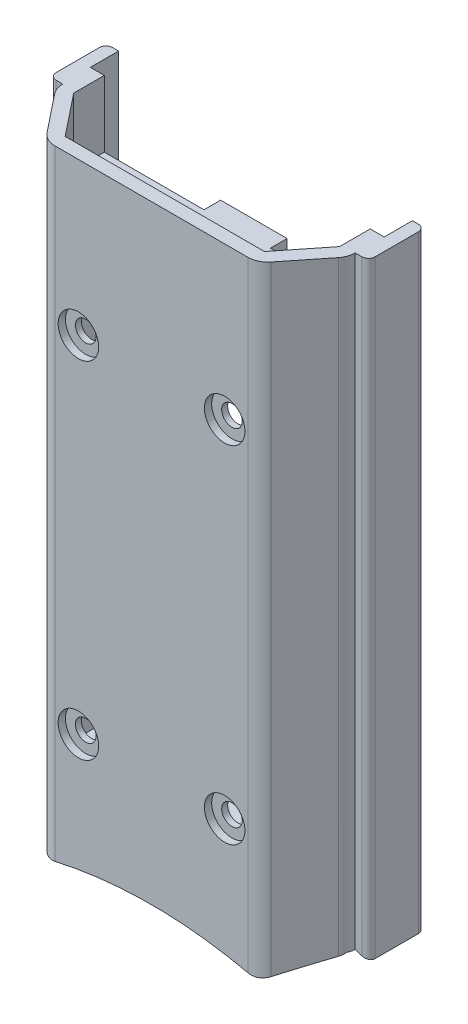
SolidWorks part; units mm, degrees
ref_plane "前视基准面" through (0, 0, 0) normal (0, 0, 1) x (1, 0, 0)
ref_plane "上视基准面" through (0, 0, 0) normal (0, 1, 0) x (1, 0, 0)
ref_plane "右视基准面" through (0, 0, 0) normal (1, 0, 0) x (0, 0, -1)
other "Configuration Table"
sketch "草图1" plane through (0, 0, 0) normal (0, 1, 0) x (1, 0, 0)
  line L5 (21.3466, -10.7196) -> (16.852, -16.3628)
  line L7 (20, -4.6001) -> (22, -4.6001)
  line L9 (20, -9.2001) -> (20, -4.6001)
  line L10 (14.9873, -15.4937) -> (20, -9.2001)
  line L11 (14.5054, -17.4937) -> (-14.5054, -17.4937)
  line L12 (-14.9873, -15.4937) -> (14.9873, -15.4937)
  line L14 (-20, -9.2001) -> (-14.9873, -15.4937)
  line L15 (-20, -4.6001) -> (-20, -9.2001)
  line L17 (-22.1, -0.3496) -> (-23, -0.3496)
  line L18 (-24, -1.3496) -> (-24, -7.8505)
  line L20 (-22, -4.6001) -> (-22.1, -4.6001)
  line L21 (-22.1, -4.6001) -> (-22.1, -0.3496)
  line L22 (22.1, -0.3496) -> (23, -0.3496)
  line L23 (24, -1.3496) -> (24, -7.8505)
  line L41 (22, -4.6001) -> (22.1, -4.6001)
  line L42 (22.1, -4.6001) -> (22.1, -0.3496)
  line L43 (-16.852, -16.3628) -> (-21.3466, -10.7196)
  line L57 (-22, -4.6001) -> (-20, -4.6001)
  line L59 (-22, -8.8505) -> (-23, -8.8505)
  line L61 (22, -8.8505) -> (23, -8.8505)
  arc A2 (23, -8.8505) -> (24, -7.8505) centre (23, -7.8505) ccw
  arc A3 (24, -1.3496) -> (23, -0.3496) centre (23, -1.3496) ccw
  arc A12 (16.852, -16.3628) -> (14.5054, -17.4937) centre (14.5054, -14.4937) cw
  arc A14 (-14.5054, -17.4937) -> (-16.852, -16.3628) centre (-14.5054, -14.4937) cw
  arc A16 (-23, -8.8505) -> (-24, -7.8505) centre (-23, -7.8505) cw
  arc A17 (-23, -0.3496) -> (-24, -1.3496) centre (-23, -1.3496) ccw
  arc A19 (21.3466, -10.7196) -> (22, -8.8505) centre (19, -8.8505) ccw
  arc A20 (-22, -8.8505) -> (-21.3466, -10.7196) centre (-19, -8.8505) ccw
  dimension "D3" = 0.1
  dimension "D2" = 0.1
extrude "凸台-拉伸1" add sketch "草图1" along normal up to surface (58.8974 mm away)
sketch "草图2" plane through (0, 0, 0) normal (0, -1, 0) x (1, 0, 0)
  line L18 (23, 8.8505) -> (22, 8.8505)
  line L19 (-24, 7.8505) -> (-24, 1.3496)
  line L20 (-23, 0.3496) -> (-22.1, 0.3496)
  line L21 (-22.1, 0.3496) -> (-22.1, 4.6001)
  line L22 (-22.1, 4.6001) -> (-20, 4.6001)
  line L23 (-20, 4.6001) -> (-20, 9.2001)
  line L24 (-20, 9.2001) -> (-14.9873, 15.4937)
  line L25 (-14.9873, 15.4937) -> (14.9873, 15.4937)
  line L26 (14.9873, 15.4937) -> (20, 9.2001)
  line L27 (20, 9.2001) -> (20, 4.6001)
  line L28 (20, 4.6001) -> (22.1, 4.6001)
  line L29 (22.1, 4.6001) -> (22.1, 0.3496)
  line L30 (22.1, 0.3496) -> (23, 0.3496)
  line L31 (24, 1.3496) -> (24, 7.8505)
  line L32 (23, 8.8505) -> (22, 8.8505)
  line L33 (21.3466, 10.7196) -> (16.852, 16.3628)
  line L34 (14.5054, 17.4937) -> (-14.5054, 17.4937)
  line L37 (-24, 7.8505) -> (-24, 1.3496)
  line L38 (-23, 0.3496) -> (-22.1, 0.3496)
  line L39 (-22.1, 0.3496) -> (-22.1, 4.6001)
  line L40 (-22.1, 4.6001) -> (-20, 4.6001)
  line L41 (-20, 4.6001) -> (-20, 9.2001)
  line L42 (-20, 9.2001) -> (-14.9873, 15.4937)
  line L43 (-14.9873, 15.4937) -> (14.9873, 15.4937)
  line L44 (14.9873, 15.4937) -> (20, 9.2001)
  line L45 (20, 9.2001) -> (20, 4.6001)
  line L46 (20, 4.6001) -> (22.1, 4.6001)
  line L47 (22.1, 4.6001) -> (22.1, 0.3496)
  line L48 (22.1, 0.3496) -> (23, 0.3496)
  line L49 (24, 1.3496) -> (24, 7.8505)
  line L51 (21.3466, 10.7196) -> (16.852, 16.3628)
  line L52 (14.5054, 17.4937) -> (-14.5054, 17.4937)
  line L57 (-16.852, 16.3628) -> (-21.3466, 10.7196)
  line L58 (-16.852, 16.3628) -> (-21.3466, 10.7196)
  line L61 (-22, 8.8505) -> (-23, 8.8505)
  line L62 (-22, 8.8505) -> (-23, 8.8505)
  arc A8 (-21.3466, 10.7196) -> (-22, 8.8505) centre (-19, 8.8505) ccw
  arc A9 (-21.3466, 10.7196) -> (-22, 8.8505) centre (-19, 8.8505) ccw
  arc A10 (22, 8.8505) -> (21.3466, 10.7196) centre (19, 8.8505) ccw
  arc A11 (22, 8.8505) -> (21.3466, 10.7196) centre (19, 8.8505) ccw
  arc A12 (-23, 8.8505) -> (-24, 7.8505) centre (-23, 7.8505) ccw
  arc A13 (-24, 1.3496) -> (-23, 0.3496) centre (-23, 1.3496) ccw
  arc A14 (23, 0.3496) -> (24, 1.3496) centre (23, 1.3496) ccw
  arc A15 (24, 7.8505) -> (23, 8.8505) centre (23, 7.8505) ccw
  arc A18 (16.852, 16.3628) -> (14.5054, 17.4937) centre (14.5054, 14.4937) ccw
  arc A19 (-14.5054, 17.4937) -> (-16.852, 16.3628) centre (-14.5054, 14.4937) ccw
  arc A22 (-23, 8.8505) -> (-24, 7.8505) centre (-23, 7.8505) ccw
  arc A23 (-24, 1.3496) -> (-23, 0.3496) centre (-23, 1.3496) ccw
  arc A24 (23, 0.3496) -> (24, 1.3496) centre (23, 1.3496) ccw
  arc A25 (24, 7.8505) -> (23, 8.8505) centre (23, 7.8505) ccw
  arc A28 (16.852, 16.3628) -> (14.5054, 17.4937) centre (14.5054, 14.4937) ccw
  arc A29 (-14.5054, 17.4937) -> (-16.852, 16.3628) centre (-14.5054, 14.4937) ccw
  dimension "D1" = 0
extrude "凸台-拉伸2" add sketch "草图2" along normal up to surface (38.3996 mm away)
ref_plane "基准面1" through (0, -38.3996, 0) normal (0, -1, 0) x (-1, 0, 0)
sketch "草图3" plane through (0, 0, 4.6001) normal (0, 0, -1) x (-1, 0, 0)
  line L0 (22.1, -38.3996) -> (22.1, -35.3996)
  line L1 (22.1, 58.8974) -> (22.1, -38.3996) construction
  line L2 (22.1, -35.3996) -> (-22.1, -35.3996)
  line L3 (-22.1, 58.8974) -> (-22.1, -38.3996) construction
  line L4 (-22.1, -35.3996) -> (-22.1, -38.3996)
  line L5 (-22.1, -38.3996) -> (22.1, -38.3996)
  dimension "D1" = 3
extrude "凸台-拉伸3" add sketch "草图3" against normal up to surface (12.8937 mm away) up to face at (0, 10.2489, 17.4937)
sketch "草图4" plane through (0, 0, 4.6001) normal (0, 0, -1) x (-1, 0, 0)
  line L0 (22.1, 38.8974) -> (-22.1, 38.8974)
  line L3 (22.1, 58.8974) -> (22.1, -38.3996) construction
  line L4 (22.1, 38.8974) -> (22.1, 35.8974)
  line L7 (-22.1, 58.8974) -> (-22.1, -38.3996) construction
  line L8 (-22.1, 38.8974) -> (-22.1, 35.8974)
  line L9 (-22.1, 35.8974) -> (22.1, 35.8974)
  dimension "D2" = 3
extrude "凸台-拉伸4" add sketch "草图4" against normal up to surface (12.8937 mm away) up to face at (0, -12.5754, 17.4937)
sketch "草图5" plane through (0, 38.8974, 0) normal (0, 1, 0) x (1, 0, 0)
  line L3 (-22, -8.8505) -> (-22.1, -8.8505)
  line L4 (-22.1, -8.8505) -> (-22.1, -17.4937)
  line L5 (-22.1, -17.4937) -> (-14.5054, -17.4937)
  line L7 (-22.1, -8.8505) -> (-22.1, -17.4937)
  line L8 (-22.1, -17.4937) -> (-14.5054, -17.4937)
  line L9 (14.5054, -17.4937) -> (22.1, -17.4937)
  line L10 (22.1, -17.4937) -> (22.1, -8.8505)
  line L11 (21.3466, -10.7196) -> (16.852, -16.3628)
  line L12 (14.5054, -17.4937) -> (22.1, -17.4937)
  line L13 (22.1, -17.4937) -> (22.1, -8.8505)
  line L14 (21.3466, -10.7196) -> (16.852, -16.3628)
  line L17 (-22, -8.8505) -> (-22.1, -8.8505)
  line L18 (-16.852, -16.3628) -> (-21.3466, -10.7196)
  line L19 (-16.852, -16.3628) -> (-21.3466, -10.7196)
  line L22 (22.1, -8.8505) -> (22, -8.8505)
  line L23 (22.1, -8.8505) -> (22, -8.8505)
  arc A2 (-22, -8.8505) -> (-21.3466, -10.7196) centre (-19, -8.8505) ccw
  arc A3 (-16.852, -16.3628) -> (-14.5054, -17.4937) centre (-14.5054, -14.4937) ccw
  arc A4 (-22, -8.8505) -> (-21.3466, -10.7196) centre (-19, -8.8505) ccw
  arc A5 (21.3466, -10.7196) -> (22, -8.8505) centre (19, -8.8505) ccw
  arc A6 (-16.852, -16.3628) -> (-14.5054, -17.4937) centre (-14.5054, -14.4937) ccw
  arc A9 (14.5054, -17.4937) -> (16.852, -16.3628) centre (14.5054, -14.4937) ccw
  arc A10 (21.3466, -10.7196) -> (22, -8.8505) centre (19, -8.8505) ccw
  arc A12 (14.5054, -17.4937) -> (16.852, -16.3628) centre (14.5054, -14.4937) ccw
  dimension "D1" = 0
  dimension "D2" = 0
extrude "切除-拉伸1" cut sketch "草图5" against normal up to surface (77.297 mm away) contours A6 L8 L7 L17 A4 L19 | A12 L14 A10 L23 L13 L12 up to face at (0, -38.3996, 6.2118)
sketch "草图6" plane through (0, 38.8974, 0) normal (0, 1, 0) x (1, 0, 0)
  line L12 (8.0613, -11.7949) -> (8.0613, -7.4001)
  line L13 (8.0613, -7.4001) -> (-8.0613, -7.4001)
  line L14 (-8.0613, -7.4001) -> (-8.0613, -11.7949)
  line L15 (-8.0613, -11.7949) -> (8.0613, -11.7949)
extrude "切除-拉伸2" cut sketch "草图6" against normal up to surface (3 mm away) up to face at (0, 35.8974, 9.7646)
sketch "草图7" plane through (0, -38.3996, 0) normal (0, -1, 0) x (-1, 0, 0)
  line L20 (20, -4.6001) -> (20, -9.2001)
  line L21 (22, -4.6001) -> (20, -4.6001)
  line L22 (22.1, -4.6001) -> (22, -4.6001)
  line L23 (22.1, -0.3496) -> (22.1, -4.6001)
  line L24 (23, -0.3496) -> (22.1, -0.3496)
  line L25 (24, -7.8505) -> (24, -1.3496)
  line L26 (22, -8.8505) -> (23, -8.8505)
  line L27 (16.852, -16.3628) -> (21.3466, -10.7196)
  line L28 (-14.5054, -17.4937) -> (14.5054, -17.4937)
  line L29 (-21.3466, -10.7196) -> (-16.852, -16.3628)
  line L30 (-23, -8.8505) -> (-22, -8.8505)
  line L31 (-24, -1.3496) -> (-24, -7.8505)
  line L32 (-22.1, -0.3496) -> (-23, -0.3496)
  line L33 (-22.1, -4.6001) -> (-22.1, -0.3496)
  line L34 (-22, -4.6001) -> (-22.1, -4.6001)
  line L35 (-20, -4.6001) -> (-22, -4.6001)
  line L36 (-20, -9.2001) -> (-20, -4.6001)
  line L37 (-14.9873, -15.4937) -> (-20, -9.2001)
  line L38 (14.9873, -15.4937) -> (-14.9873, -15.4937)
  line L39 (20, -9.2001) -> (14.9873, -15.4937)
  line L40 (20, -4.6001) -> (20, -9.2001)
  line L41 (22, -4.6001) -> (20, -4.6001)
  line L42 (22.1, -4.6001) -> (22, -4.6001)
  line L43 (22.1, -0.3496) -> (22.1, -4.6001)
  line L44 (23, -0.3496) -> (22.1, -0.3496)
  line L45 (24, -7.8505) -> (24, -1.3496)
  line L46 (22, -8.8505) -> (23, -8.8505)
  line L47 (16.852, -16.3628) -> (21.3466, -10.7196)
  line L48 (-14.5054, -17.4937) -> (14.5054, -17.4937)
  line L49 (-21.3466, -10.7196) -> (-16.852, -16.3628)
  line L50 (-23, -8.8505) -> (-22, -8.8505)
  line L51 (-24, -1.3496) -> (-24, -7.8505)
  line L52 (-22.1, -0.3496) -> (-23, -0.3496)
  line L53 (-22.1, -4.6001) -> (-22.1, -0.3496)
  line L54 (-22, -4.6001) -> (-22.1, -4.6001)
  line L55 (-20, -4.6001) -> (-22, -4.6001)
  line L56 (-20, -9.2001) -> (-20, -4.6001)
  line L57 (-14.9873, -15.4937) -> (-20, -9.2001)
  line L58 (14.9873, -15.4937) -> (-14.9873, -15.4937)
  line L59 (20, -9.2001) -> (14.9873, -15.4937)
  arc A8 (24, -1.3496) -> (23, -0.3496) centre (23, -1.3496) ccw
  arc A9 (23, -8.8505) -> (24, -7.8505) centre (23, -7.8505) ccw
  arc A10 (21.3466, -10.7196) -> (22, -8.8505) centre (19, -8.8505) ccw
  arc A11 (14.5054, -17.4937) -> (16.852, -16.3628) centre (14.5054, -14.4937) ccw
  arc A12 (-16.852, -16.3628) -> (-14.5054, -17.4937) centre (-14.5054, -14.4937) ccw
  arc A13 (-22, -8.8505) -> (-21.3466, -10.7196) centre (-19, -8.8505) ccw
  arc A14 (-24, -7.8505) -> (-23, -8.8505) centre (-23, -7.8505) ccw
  arc A15 (-23, -0.3496) -> (-24, -1.3496) centre (-23, -1.3496) ccw
  arc A16 (24, -1.3496) -> (23, -0.3496) centre (23, -1.3496) ccw
  arc A17 (23, -8.8505) -> (24, -7.8505) centre (23, -7.8505) ccw
  arc A18 (21.3466, -10.7196) -> (22, -8.8505) centre (19, -8.8505) ccw
  arc A19 (14.5054, -17.4937) -> (16.852, -16.3628) centre (14.5054, -14.4937) ccw
  arc A20 (-16.852, -16.3628) -> (-14.5054, -17.4937) centre (-14.5054, -14.4937) ccw
  arc A21 (-22, -8.8505) -> (-21.3466, -10.7196) centre (-19, -8.8505) ccw
  arc A22 (-24, -7.8505) -> (-23, -8.8505) centre (-23, -7.8505) ccw
  arc A23 (-23, -0.3496) -> (-24, -1.3496) centre (-23, -1.3496) ccw
  dimension "D1" = 0
extrude "凸台-拉伸5" add sketch "草图7" along normal blind 15
sketch "草图8" plane through (0, 0, 0) normal (1, 0, 0) x (0, 0, -1)
  line L14 (-9.8992, -38.2996) -> (-20.2915, -44.2996)
  line L18 (-9.8992, -40.3996) -> (-9.8992, -176.3996) construction
  line L19 (-20.2915, -44.3996) -> (-20.2915, -172.3996) construction
  line L20 (-20.2915, -44.2996) -> (-20.2915, -55.8019)
  line L21 (-9.8992, -108.3996) -> (14.8215, -108.3996) construction
  line L22 (-20.2915, -46.3996) -> (-20.2915, -170.3996) construction
  line L23 (-20.2915, -55.8019) -> (11.0914, -55.8019)
  line L25 (0.6991, -38.2996) -> (-9.8992, -38.2996)
  line L26 (-4.6001, 35.8974) -> (-4.6001, -35.3996) construction
  line L27 (11.0914, -44.2996) -> (11.0914, -55.8019)
  line L28 (0.6991, -38.2996) -> (11.0914, -44.2996)
revolve "切除-旋转1" cut sketch "草图8" angle 360 about L21
sketch "草图11" plane through (0, 0, 17.4937) normal (0, 0, 1) x (1, 0, 0)
  circle A0 centre (-11, 26.0001) radius 3.05
  circle A1 centre (11, 26.0001) radius 3.05
  circle A2 centre (-11, -26.0001) radius 3.05
  circle A3 centre (11, -26.0001) radius 3.05
extrude "切除-拉伸4" cut sketch "草图11" against normal blind 1.1
sketch "草图13" plane through (0, 58.8974, 0) normal (0, 1, 0) x (1, 0, 0)
  line L18 (-23, -8.8505) -> (-22, -8.8505)
  line L19 (-21.3466, -10.7196) -> (-16.852, -16.3628)
  line L20 (-14.5054, -17.4937) -> (14.5054, -17.4937)
  line L21 (16.852, -16.3628) -> (21.3466, -10.7196)
  line L22 (22, -8.8505) -> (23, -8.8505)
  line L23 (24, -7.8505) -> (24, -1.3496)
  line L24 (23, -0.3496) -> (22.1, -0.3496)
  line L25 (22.1, -0.3496) -> (22.1, -4.6001)
  line L26 (22.1, -4.6001) -> (20, -4.6001)
  line L27 (20, -4.6001) -> (20, -9.2001)
  line L28 (20, -9.2001) -> (14.9873, -15.4937)
  line L29 (14.9873, -15.4937) -> (-14.9873, -15.4937)
  line L30 (-14.9873, -15.4937) -> (-20, -9.2001)
  line L31 (-20, -9.2001) -> (-20, -4.6001)
  line L32 (-20, -4.6001) -> (-22.1, -4.6001)
  line L33 (-22.1, -4.6001) -> (-22.1, -0.3496)
  line L34 (-22.1, -0.3496) -> (-23, -0.3496)
  line L35 (-24, -1.3496) -> (-24, -7.8505)
  line L36 (-23, -8.8505) -> (-22, -8.8505)
  line L37 (-21.3466, -10.7196) -> (-16.852, -16.3628)
  line L38 (-14.5054, -17.4937) -> (14.5054, -17.4937)
  line L39 (16.852, -16.3628) -> (21.3466, -10.7196)
  line L40 (22, -8.8505) -> (23, -8.8505)
  line L41 (24, -7.8505) -> (24, -1.3496)
  line L42 (23, -0.3496) -> (22.1, -0.3496)
  line L43 (22.1, -0.3496) -> (22.1, -4.6001)
  line L44 (22.1, -4.6001) -> (20, -4.6001)
  line L45 (20, -4.6001) -> (20, -9.2001)
  line L46 (20, -9.2001) -> (14.9873, -15.4937)
  line L47 (14.9873, -15.4937) -> (-14.9873, -15.4937)
  line L48 (-14.9873, -15.4937) -> (-20, -9.2001)
  line L49 (-20, -9.2001) -> (-20, -4.6001)
  line L50 (-20, -4.6001) -> (-22.1, -4.6001)
  line L51 (-22.1, -4.6001) -> (-22.1, -0.3496)
  line L52 (-22.1, -0.3496) -> (-23, -0.3496)
  line L53 (-24, -1.3496) -> (-24, -7.8505)
  arc A8 (-22, -8.8505) -> (-21.3466, -10.7196) centre (-19, -8.8505) ccw
  arc A9 (-16.852, -16.3628) -> (-14.5054, -17.4937) centre (-14.5054, -14.4937) ccw
  arc A10 (14.5054, -17.4937) -> (16.852, -16.3628) centre (14.5054, -14.4937) ccw
  arc A11 (21.3466, -10.7196) -> (22, -8.8505) centre (19, -8.8505) ccw
  arc A12 (23, -8.8505) -> (24, -7.8505) centre (23, -7.8505) ccw
  arc A13 (24, -1.3496) -> (23, -0.3496) centre (23, -1.3496) ccw
  arc A14 (-23, -0.3496) -> (-24, -1.3496) centre (-23, -1.3496) ccw
  arc A15 (-24, -7.8505) -> (-23, -8.8505) centre (-23, -7.8505) ccw
  arc A16 (-22, -8.8505) -> (-21.3466, -10.7196) centre (-19, -8.8505) ccw
  arc A17 (-16.852, -16.3628) -> (-14.5054, -17.4937) centre (-14.5054, -14.4937) ccw
  arc A18 (14.5054, -17.4937) -> (16.852, -16.3628) centre (14.5054, -14.4937) ccw
  arc A19 (21.3466, -10.7196) -> (22, -8.8505) centre (19, -8.8505) ccw
  arc A20 (23, -8.8505) -> (24, -7.8505) centre (23, -7.8505) ccw
  arc A21 (24, -1.3496) -> (23, -0.3496) centre (23, -1.3496) ccw
  arc A22 (-23, -0.3496) -> (-24, -1.3496) centre (-23, -1.3496) ccw
  arc A23 (-24, -7.8505) -> (-23, -8.8505) centre (-23, -7.8505) ccw
  dimension "D1" = 0
extrude "切除-拉伸5" cut sketch "草图13" against normal blind 10
sketch "草图14" plane through (0, 0, 16.3937) normal (0, 0, 1) x (1, 0, 0)
  circle A0 centre (-11, 26.0001) radius 1.55
  circle A1 centre (11, 26.0001) radius 1.55
  circle A2 centre (-11, -26.0001) radius 1.55
  circle A3 centre (11, -26.0001) radius 1.55
extrude "切除-拉伸6" cut sketch "草图14" against normal through all
sketch "草图15" plane through (0, 0, 11.7949) normal (0, 0, -1) x (-1, 0, 0)
  line L4 (8.0613, 35.8974) -> (8.0613, 38.8974)
  line L5 (8.0613, 38.8974) -> (-8.0613, 38.8974)
  line L6 (-8.0613, 38.8974) -> (-8.0613, 35.8974)
  line L7 (-8.0613, 35.8974) -> (8.0613, 35.8974)
  line L8 (8.0613, 35.8974) -> (8.0613, 38.8974)
  line L9 (8.0613, 38.8974) -> (-8.0613, 38.8974)
  line L10 (-8.0613, 38.8974) -> (-8.0613, 35.8974)
  line L11 (-8.0613, 35.8974) -> (8.0613, 35.8974)
  dimension "D1" = 0
extrude "切除-拉伸7" cut sketch "草图15" against normal blind 0.5
sketch "草图16" plane through (0, 0, 4.6001) normal (0, 0, -1) x (-1, 0, 0)
  line L0 (-5, 38.8974) -> (5, 38.8974)
  line L1 (20, 38.8974) -> (-20, 38.8974) construction
  line L2 (5, 38.8974) -> (5, 35.8974)
  line L3 (14.9873, 35.8974) -> (-14.9873, 35.8974) construction
  line L4 (5, 35.8974) -> (-5, 35.8974)
  line L5 (-5, 35.8974) -> (-5, 38.8974)
  point P5 (0, 38.8974)
extrude "凸台-拉伸6" add sketch "草图16" along normal blind 2.5
sketch "草图17" plane through (0, 0, 15.4937) normal (0, 0, -1) x (-1, 0, 0)
  line L0 (-7.2, 40.6974) -> (-7.2, 46.0974)
  line L6 (-7.2, 46.0974) -> (7.2, 46.0974)
  line L7 (7.2, 46.0974) -> (7.2, 40.6974)
  line L8 (7.2, 40.6974) -> (-7.2, 40.6974)
  point P5 (0, 48.8974)
extrude "切除-拉伸8" cut sketch "草图17" against normal blind 1
